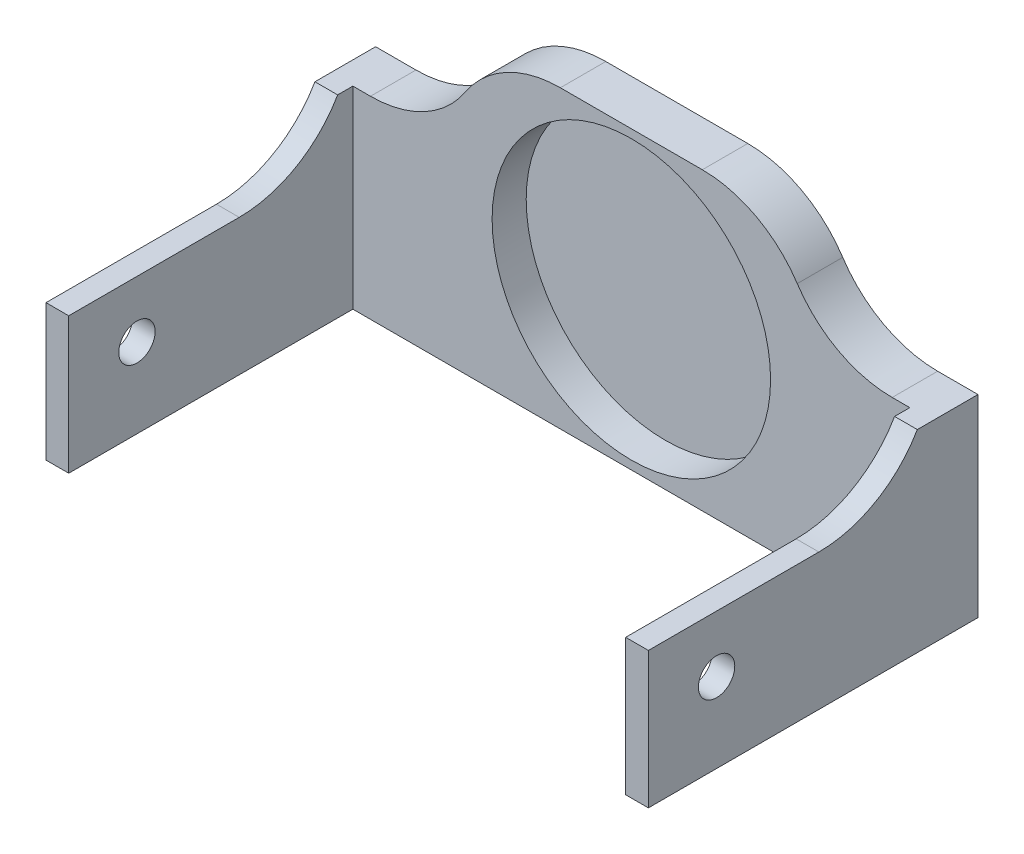
SolidWorks part; units mm, degrees
ref_plane "Front Plane" through (0, 0, 0) normal (0, 0, 1) x (1, 0, 0)
ref_plane "Top Plane" through (0, 0, 0) normal (0, 1, 0) x (1, 0, 0)
ref_plane "Right Plane" through (0, 0, 0) normal (1, 0, 0) x (0, 0, -1)
sketch "Sketch1" plane through (0, 0, 0) normal (0, 0, 1) x (1, 0, 0)
  line L1 (-6.8332, 6.2473) -> (46.1668, 6.2473)
  line L2 (-6.8332, 6.2473) -> (-6.8332, -19.7527)
  line L3 (-6.8332, -19.7527) -> (46.1668, -19.7527)
  line L4 (46.1668, 6.2473) -> (46.1668, -19.7527)
  dimension "D1" = 53
  dimension "D2" = 26
extrude "Boss-Extrude2" add sketch "Sketch1" along normal blind 4
sketch "Sketch3" plane through (0, 0, 4) normal (0, 0, 1) x (1, 0, 0)
  line L0 (46.1668, 6.2473) -> (-6.8332, 6.2473) construction
  line L1 (-6.8332, 6.2473) -> (-6.8332, -19.7527) construction
  circle A0 centre (19.6668, -6.7527) radius 12.25
  dimension "D1" = 24.5
  dimension "D2" = 13
  dimension "D3" = 26.5
extrude "Cut-Extrude2" cut sketch "Sketch3" against normal blind 3
sketch "Sketch4" plane through (0, 0, 4) normal (0, 0, 1) x (1, 0, 0)
  line L0 (-6.8332, -19.7527) -> (46.1668, -19.7527) construction
  line L1 (-6.8332, 6.2473) -> (6.6668, 6.2473)
  line L2 (-6.8332, 6.2473) -> (-6.8332, -2.7527)
  line L3 (-6.8332, -2.7527) -> (6.6668, -2.7527)
  line L4 (6.6668, 6.2473) -> (6.6668, -2.7527)
  line L5 (46.1668, 6.2473) -> (-6.8332, 6.2473) construction
  line L6 (19.6668, 6.2473) -> (19.6668, -27.0994) construction
  line L7 (46.1668, -2.7527) -> (32.6668, -2.7527)
  line L8 (32.6668, 6.2473) -> (32.6668, -2.7527)
  line L9 (46.1668, 6.2473) -> (32.6668, 6.2473)
  line L10 (46.1668, 6.2473) -> (46.1668, -2.7527)
  point P9 (19.6668, 6.2473)
  dimension "D1" = 17
  dimension "D2" = 13
extrude "Cut-Extrude3" cut sketch "Sketch4" against normal up to next
fillet "Fillet1" radius 10 2 edges at (32.6668, -2.7527, 2) (6.6668, -2.7527, 2)
fillet "Fillet2" radius 10 2 edges at (32.6668, 6.2473, 2) (6.6668, 6.2473, 2)
sketch "Sketch5" plane through (0, 0, 4) normal (0, 0, 1) x (1, 0, 0)
  line L0 (-6.8332, -19.7527) -> (46.1668, -19.7527) construction
  line L1 (-6.8332, -7.7527) -> (-4.8332, -7.7527)
  line L2 (-6.8332, -7.7527) -> (-6.8332, -19.7527)
  line L3 (-6.8332, -19.7527) -> (-4.8332, -19.7527)
  line L4 (-4.8332, -7.7527) -> (-4.8332, -19.7527)
  line L5 (19.6668, 6.2473) -> (19.6668, -25.1126) construction
  line L10 (25.9134, 6.2473) -> (13.4203, 6.2473) construction
  line L11 (46.1668, -19.7527) -> (44.1668, -19.7527)
  line L12 (44.1668, -7.7527) -> (44.1668, -19.7527)
  line L13 (46.1668, -7.7527) -> (44.1668, -7.7527)
  line L14 (46.1668, -7.7527) -> (46.1668, -19.7527)
  line L15 (-6.8332, -2.7527) -> (-6.8332, -19.7527) construction
  dimension "D1" = 2
  dimension "D3" = 12
extrude "Boss-Extrude3" add sketch "Sketch5" along normal blind 25
sketch "Sketch6" plane through (-6.8332, 0, 0) normal (-1, 0, 0) x (0, 0, 1)
  line L0 (29, -19.7527) -> (0, -19.7527) construction
  line L1 (29, -7.7527) -> (29, -19.7527) construction
  circle A0 centre (23, -12.7527) radius 1.6
  dimension "D1" = 7
  dimension "D2" = 6
  dimension "D3" = 3.2
extrude "Cut-Extrude4" cut sketch "Sketch6" against normal through all
fillet "Fillet3" radius 10 2 edges at (45.1668, -7.7527, 4) (-5.8332, -7.7527, 4)
